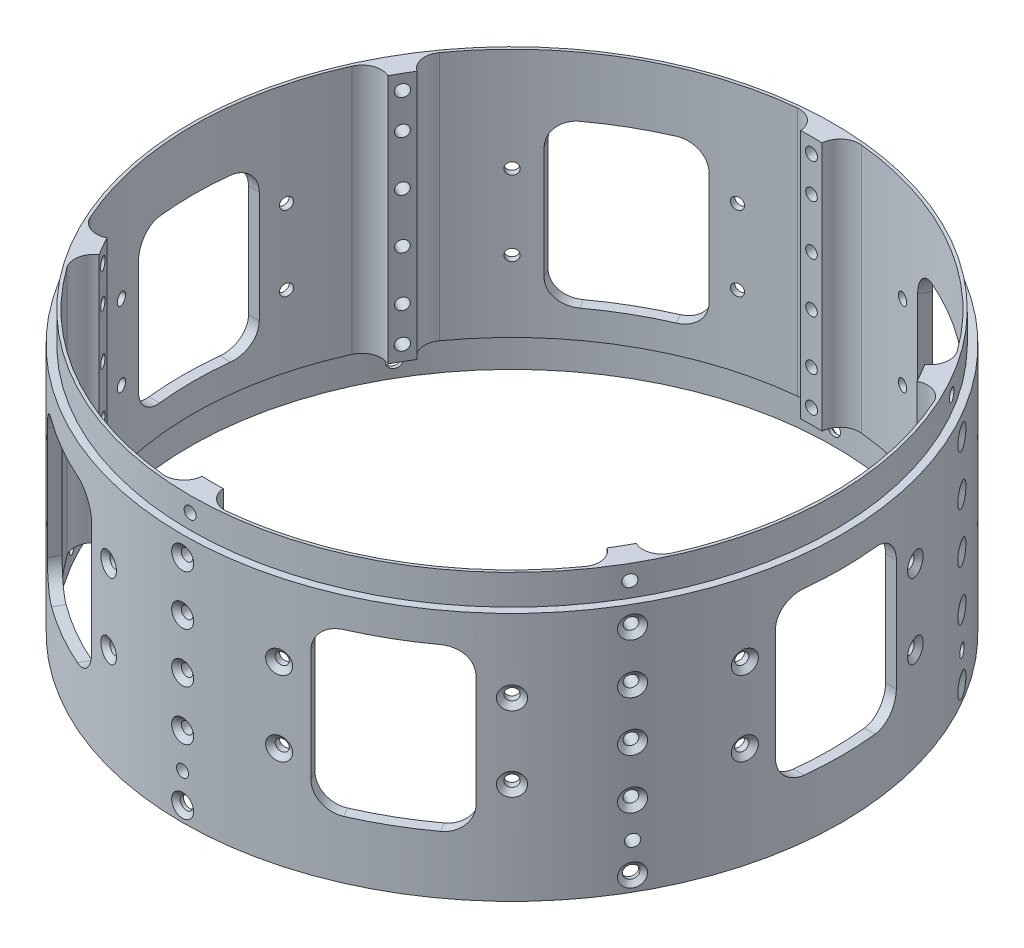
SolidWorks part; units mm, degrees
material "6061-T6 (SS)"
ref_plane "Front Plane" through (0, 0, 0) normal (0, 0, 1) x (1, 0, 0)
ref_plane "Top Plane" through (0, 0, 0) normal (0, 1, 0) x (1, 0, 0)
ref_plane "Right Plane" through (0, 0, 0) normal (1, 0, 0) x (0, 0, -1)
sketch "Sketch1" plane through (0, 0, 0) normal (0, 0, 1) x (1, 0, 0)
  line L0 (0, 42.3951) -> (0, -32.8937) construction
  line L1 (0, -35.6235) -> (0, 35.6235) construction
  line L2 (76.2, -63.5) -> (76.2, 0)
  line L3 (76.2, 0) -> (81.8896, 0)
  line L4 (81.8896, 0) -> (81.8896, -7.6708)
  line L5 (81.8896, -7.6708) -> (83.82, -7.6708)
  line L6 (83.82, -7.6708) -> (83.82, -71.12)
  line L7 (83.82, -71.12) -> (81.9404, -71.12)
  line L8 (81.9404, -71.12) -> (81.9404, -63.5)
  line L9 (81.9404, -63.5) -> (76.2, -63.5)
  line L10 (81.8896, -7.62) -> (84.2911, -7.62) construction
  dimension "D5" = 5.6896
  dimension "D10" = 76.2
  dimension "D2" = 7.62
  dimension "D4" = 7.62
  dimension "D6" = 7.62
revolve "Revolve1" add sketch "Sketch1" angle 360 about L0
sketch "Sketch2" plane through (0, 0, 0) normal (0, 1, 0) x (1, 0, 0)
  line L0 (0, 0) -> (0, 112.6688) construction
  line L1 (0, -35.6235) -> (0, 35.6235) construction
  line L2 (0, 0) -> (-128.6689, 74.287) construction
  line L3 (0, 0) -> (-50.2561, 87.0461) construction
  line L4 (0, 0) -> (-7.6343, 75.8166) construction
  arc A0 (-7.6343, 75.8166) -> (-61.8419, 44.5198) centre (0, 0) ccw construction
  arc A1 (-8.128, 80.7194) -> (-65.841, 47.3988) centre (0, 0) ccw
  arc A2 (-7.1406, 70.9138) -> (-57.8428, 41.6409) centre (0, 0) ccw
  arc A3 (-7.1406, 70.9138) -> (-8.128, 80.7194) centre (-7.6343, 75.8166) ccw
  arc A4 (-65.841, 47.3988) -> (-57.8428, 41.6409) centre (-61.8419, 44.5198) ccw
  circle A5 centre (0, 0) radius 81.8896 construction
  circle A7 centre (0, 0) radius 76.2 construction
  point P5 (-38.1, 65.9911)
  dimension "D2" = 0.762
  dimension "D1" = 60
  dimension "D3" = 30
  dimension "D4" = 5.75
extrude "Cut-Extrude1" cut sketch "Sketch2" against normal through all
pattern_circular "CirPattern1" count 6 over 360 about axis through (0, 42.3951, 0) along (0, 1, 0) of "Cut-Extrude1"
ref_plane "Plane1" through (0, 0, 83.82) normal (0, 0, 1) x (1, 0, 0)
hole_wizard "Tapped Hole for #4-40 Helicoil1" positions "Sketch3" profile "Sketch4" tap size "#4-40" standard "Helicoil® Inch"
sketch "Sketch3" plane through (0, 0, 83.82) normal (0, 0, 1) x (1, 0, 0)
  line L0 (81.8896, 0) -> (-81.8896, 0) construction
  line L1 (2.7181, 0) -> (-2.7181, 0) construction
  line L2 (2.7181, 0) -> (-2.7181, 0) construction
  line L3 (0, 0) -> (0, -3.81) construction
  line L5 (-2.7181, -63.5) -> (2.7181, -63.5) construction
  line L6 (-2.7181, -63.5) -> (2.7181, -63.5) construction
  line L7 (0, -63.5) -> (0, -59.69) construction
  point P0 (0, -3.81)
  point P20 (0, -59.69)
  dimension "D1" = 3.81
  dimension "D2" = 3.81
cosmetic thread "Hole Thread1" parameters "D1"=3.556, "D2"=3.7414
cosmetic thread "Hole Thread6" parameters "D1"=3.556, "D2"=3.7414
sketch "Sketch4" plane through (0, -3.81, 83.82) normal (1, 0, 0) x (0, -1, 0)
  line L0 (0, 0) -> (0, 26.3157)
  line L1 (0, 26.3157) -> (1.524, 25.4)
  line L2 (1.524, 25.4) -> (1.524, 0)
  line L5 (1.524, 0) -> (0, 0)
  line L10 (0, 26.3157) -> (-1.524, 25.4) construction
  line L11 (0, -6.35) -> (0, 107.95) construction
  dimension "Tap Drill Dia." = 3.048
  dimension "Tap Drill Depth" = 25.4
  dimension "Drill Angle" = 118
hole_wizard "CSK for #4 Flat Head Machine Screw (100)1" positions "Sketch5" profile "Sketch6" countersink size "#4" standard "ANSI Inch"
sketch "Sketch5" plane through (0, 0, 83.82) normal (0, 0, 1) x (1, 0, 0)
  line L0 (-2.7181, -63.5) -> (2.7181, -63.5) construction
  line L1 (-2.7181, -63.5) -> (2.7181, -63.5) construction
  line L2 (0, -63.5) -> (0, -67.31) construction
  point P0 (0, -67.31)
  dimension "D1" = 3.81
sketch "Sketch6" plane through (0, -67.31, 83.82) normal (1, 0, 0) x (0, -1, 0)
  line L0 (0, 0) -> (0, 26.3806)
  line L1 (0, 26.3806) -> (1.6319, 25.4)
  line L2 (1.6319, 25.4) -> (1.6319, 1.0284)
  line L3 (1.6319, 1.0284) -> (2.8575, 0)
  line L5 (2.8575, 0) -> (0, 0)
  line L6 (-1.6319, 1.0284) -> (-2.8575, 0) construction
  line L10 (0, 26.3806) -> (-1.632, 25.4) construction
  line L11 (0, -6.35) -> (0, 107.95) construction
  dimension "Hole Dia." = 3.2639
  dimension "Hole Depth" = 25.4
  dimension "Near C'Sink Dia." = 5.715
  dimension "Near C'Sink Angle" = 100
  dimension "Drill Angle" = 118
hole_wizard "CSK for #4 Flat Head Machine Screw (100)3" positions "Sketch12" profile "Sketch13" countersink size "#4" standard "ANSI Inch"
sketch "Sketch12" plane through (0, 0, 83.82) normal (0, 0, 1) x (1, 0, 0)
  line L0 (-2.7181, -63.5) -> (2.7181, -63.5) construction
  line L1 (0, -12.7) -> (0, -38.1) construction
  line L2 (0, -38.1) -> (0, -63.5) construction
  point P0 (0, -38.1)
  point P2 (0, -12.7)
  point P6 (0, -63.5)
  point P7 (0, -25.4)
  point P9 (0, -50.8)
  dimension "D1" = 25.4
  dimension "D2" = 50.8
sketch "Sketch13" plane through (0, -38.1, 83.82) normal (1, 0, 0) x (0, -1, 0)
  line L0 (0, 0) -> (0, 26.2852)
  line L1 (0, 26.2852) -> (1.4732, 25.4)
  line L2 (1.4732, 25.4) -> (1.4732, 1.1616)
  line L3 (1.4732, 1.1616) -> (2.8575, 0)
  line L5 (2.8575, 0) -> (0, 0)
  line L6 (-1.4732, 1.1616) -> (-2.8575, 0) construction
  line L10 (0, 26.2852) -> (-1.4732, 25.4) construction
  line L11 (0, -6.35) -> (0, 107.95) construction
  dimension "Hole Dia." = 2.9464
  dimension "Hole Depth" = 25.4
  dimension "Near C'Sink Dia." = 5.715
  dimension "Near C'Sink Angle" = 100
  dimension "Drill Angle" = 118
pattern_circular "CirPattern2" count 6 over 360 about axis through (0, 42.3951, 0) along (0, 1, 0) of "Tapped Hole for #4-40 Helicoil1", "CSK for #4 Flat Head Machine Screw (100)1", "CSK for #4 Flat Head Machine Screw (100)3"
sketch "Sketch7" plane through (0, 0, 0) normal (1, 0, 0) x (0, 0, -1)
  line L1 (-9.017, -15.24) -> (9.017, -15.24)
  line L2 (-15.367, -21.59) -> (-15.367, -50.038)
  line L3 (-9.017, -56.388) -> (9.017, -56.388)
  line L4 (15.367, -21.59) -> (15.367, -50.038)
  line L5 (-15.367, -15.24) -> (15.367, -56.388) construction
  line L6 (-15.367, -56.388) -> (15.367, -15.24) construction
  arc A0 (-15.367, -50.038) -> (-9.017, -56.388) centre (-9.017, -50.038) ccw
  arc A1 (9.017, -56.388) -> (15.367, -50.038) centre (9.017, -50.038) ccw
  arc A2 (15.367, -21.59) -> (9.017, -15.24) centre (9.017, -21.59) ccw
  arc A3 (-9.017, -15.24) -> (-15.367, -21.59) centre (-9.017, -21.59) ccw
  point P0 (0, -35.814)
  dimension "D4" = 6.35
  dimension "D1" = 41.148
  dimension "D2" = 30.734
  dimension "D3" = 15.24
extrude "Cut-Extrude2" cut sketch "Sketch7" against normal through all
sketch "Sketch9" plane through (0, -7.6708, 0) normal (0, 1, 0) x (1, 0, 0)
  line L0 (-49.5, 0) -> (-83.82, 0)
  line L1 (-50.2347, -13.4603) -> (-80.9639, -21.6942)
  line L2 (-83.82, 11.0351) -> (-83.82, -11.0351) construction
  line L3 (-83.82, -11.0351) -> (-78.1078, -32.3533) construction
  arc A0 (-83.3336, 9.017) -> (-83.3336, -9.017) centre (0, 0) ccw construction
  circle A1 centre (0, 0) radius 83.82 construction
  dimension "D1" = 15
ref_plane "Plane3" through (-80.9639, -7.6708, 21.6942) normal (-0.9659, 0, 0.2588) x (0.2588, 0, 0.9659)
hole_wizard "CSK for #4 Flat Head Machine Screw (100)2" positions "Sketch10" profile "Sketch11" countersink size "#4" standard "ANSI Inch"
sketch "Sketch10" plane through (-80.9639, -7.6708, 21.6942) normal (-0.9659, 0, 0.2588) x (0.2588, 0, 0.9659)
  line L0 (0, 0) -> (0, -18.6182) construction
  line L1 (0, -18.6182) -> (0, -37.6682) construction
  line L5 (0, -28.1432) -> (-6.4831, -28.1432) construction
  line L8 (-6.4831, -13.9192) -> (-6.4831, -42.3672) construction
  point P0 (0, -18.6182)
  point P2 (0, -37.6682)
  dimension "D1" = 19.05
sketch "Sketch11" plane through (-80.9639, -26.289, 21.6942) normal (0, 1, 0) x (0.2588, 0, 0.9659)
  line L0 (0, 0) -> (0, 26.2852)
  line L1 (0, 26.2852) -> (1.4732, 25.4)
  line L2 (1.4732, 25.4) -> (1.4732, 1.1616)
  line L3 (1.4732, 1.1616) -> (2.8575, 0)
  line L5 (2.8575, 0) -> (0, 0)
  line L6 (-1.4732, 1.1616) -> (-2.8575, 0) construction
  line L10 (0, 26.2852) -> (-1.4732, 25.4) construction
  line L11 (0, -6.35) -> (0, 107.95) construction
  dimension "Hole Dia." = 2.9464
  dimension "Hole Depth" = 25.4
  dimension "Near C'Sink Dia." = 5.715
  dimension "Near C'Sink Angle" = 100
  dimension "Drill Angle" = 118
mirror "Mirror1" about plane through (0, 0, 0) normal (0, 0, 1) of "CSK for #4 Flat Head Machine Screw (100)2"
pattern_circular "CirPattern5" count 6 over 360 about axis through (0, -7.6708, 0) along (0, 1, 0) of "Cut-Extrude2", "Mirror1"
ref_plane "Plane2" [suppressed] through (0, 0, 0) normal (-0.7071, 0, 0.7071) x (0.7071, 0, 0.7071)
sketch "Sketch8" [suppressed] plane through (0, 0, 0) normal (-0.7071, 0, 0.7071) x (0.7071, 0, 0.7071)
  line L0 (0, 0) -> (89.1919, 0) construction
  line L1 (-9.017, -17.145) -> (-6.858, -17.145)
  line L2 (-12.192, -20.32) -> (-12.192, -31.115)
  line L3 (-9.017, -34.29) -> (-6.858, -34.29)
  line L4 (-3.683, -20.32) -> (-3.683, -31.115)
  line L5 (0, 0) -> (0, -89.2767) construction
  line L6 (-83.82, -71.12) -> (83.82, -71.12) construction
  line L7 (-7.9375, -52.07) -> (-4.7625, -52.07)
  line L8 (-9.525, -53.6575) -> (-9.525, -56.8325)
  line L9 (-7.9375, -58.42) -> (-4.7625, -58.42)
  line L10 (-3.175, -53.6575) -> (-3.175, -56.8325)
  arc A0 (-9.017, -34.29) -> (-12.192, -31.115) centre (-9.017, -31.115) cw
  arc A1 (-3.683, -31.115) -> (-6.858, -34.29) centre (-6.858, -31.115) cw
  arc A2 (-3.683, -20.32) -> (-6.858, -17.145) centre (-6.858, -20.32) ccw
  arc A3 (-9.017, -17.145) -> (-12.192, -20.32) centre (-9.017, -20.32) ccw
  arc A4 (-9.525, -56.8325) -> (-7.9375, -58.42) centre (-7.9375, -56.8325) ccw
  arc A5 (-3.175, -56.8325) -> (-4.7625, -58.42) centre (-4.7625, -56.8325) cw
  arc A6 (-3.175, -53.6575) -> (-4.7625, -52.07) centre (-4.7625, -53.6575) ccw
  arc A7 (-7.9375, -52.07) -> (-9.525, -53.6575) centre (-7.9375, -53.6575) ccw
  circle A8 centre (-6.35, -48.895) radius 1.5875
  circle A9 centre (-6.35, -61.595) radius 1.5875
  point P20 (-3.175, -55.245)
  point P29 (-6.35, -58.42)
  dimension "D1" = 3.175
  dimension "D8" = 1.5875
  dimension "D11" = 3.175
  dimension "D12" = 3.175
  dimension "D2" = 8.509
  dimension "D3" = 17.145
  dimension "D4" = 17.145
  dimension "D5" = 3.683
  dimension "D6" = 6.35
  dimension "D7" = 6.35
  dimension "D9" = 6.35
  dimension "D10" = 12.7
  dimension "D13" = 3.175
  dimension "D14" = 3.175
extrude "Cut-Extrude3" [suppressed] cut sketch "Sketch8" along normal through all
equation "\"nominalLength\"=2.5"
equation "\"D8@Sketch1\"=\"nominalLength\""
equation "\"D12@Sketch8\"=\"D11@Sketch8\""
